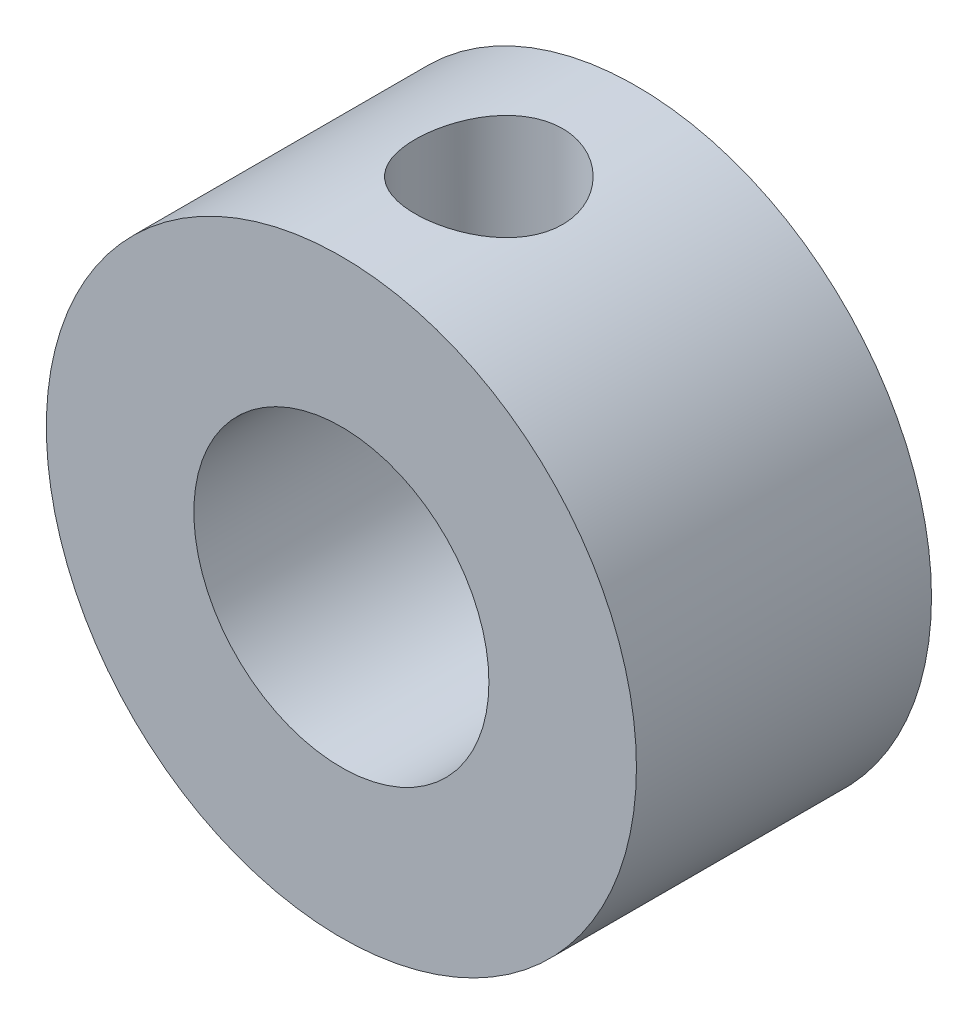
SolidWorks part; units mm, degrees
ref_plane "Front Plane" through (0, 0, 0) normal (0, 0, 1) x (1, 0, 0)
ref_plane "Top Plane" through (0, 0, 0) normal (0, 1, 0) x (1, 0, 0)
ref_plane "Right Plane" through (0, 0, 0) normal (1, 0, 0) x (0, 0, -1)
sketch "Sketch1" plane through (0, 0, 0) normal (0, 0, 1) x (1, 0, 0)
  circle A0 centre (0, 0) radius 3
  circle A1 centre (0, 0) radius 6
extrude "Boss-Extrude1" add sketch "Sketch1" along normal blind 6
sketch "PRELIMINARY" plane through (0, 0, 6) normal (0, 0, 1) x (1, 0, 0)
  arc A0 (-4, 0) -> (4, 0) centre (0, 0) cw construction
  text T0 "PRELIMINARY" font "Century Gothic" height 1
sketch "Sketch3" plane through (0, 0, 0) normal (0, 1, 0) x (1, 0, 0)
  line L5 (-0.0028, -6) -> (0, 0) construction
  circle A0 centre (-0.0014, -3) radius 1.5
  point P14 (-0.0014, -3)
extrude "Cut-Extrude1" cut sketch "Sketch3" along normal through all
